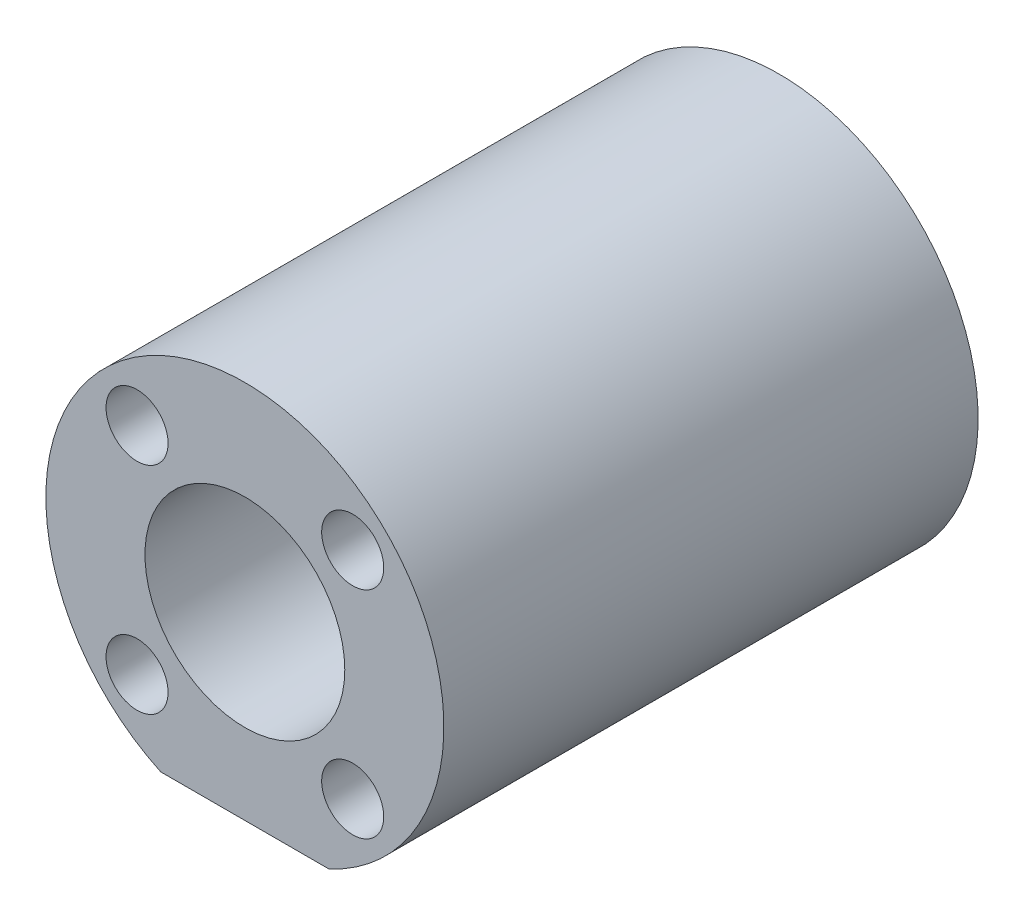
SolidWorks part; units mm, degrees
ref_plane "Front Plane" through (0, 0, 0) normal (0, 0, 1) x (1, 0, 0)
ref_plane "Top Plane" through (0, 0, 0) normal (0, 1, 0) x (1, 0, 0)
ref_plane "Right Plane" through (0, 0, 0) normal (1, 0, 0) x (0, 0, -1)
sketch "Sketch1" plane through (0, 0, 0) normal (0, 0, 1) x (1, 0, 0)
  line L0 (0, 0) -> (0, -18.584) construction
  line L1 (-3.9986, -8.575) -> (3.9986, -8.575)
  line L2 (3.9986, -8.575) -> (59.8984, 17.4915) construction
  arc A0 (-3.9986, -8.575) -> (3.9986, -8.575) centre (0, 0) cw
  circle A1 centre (0, 0) radius 4.75
  dimension "D2" = 9.4615
  dimension "D4" = 9.5
  dimension "D1" = 25
  dimension "D3" = 8.575
extrude "Boss-Extrude1" add sketch "Sketch1" along normal blind 25.4
sketch "Sketch3" plane through (0, 0, 25.4) normal (0, 0, -1) x (-1, 0, 0)
  line L0 (0, 0) -> (5.1265, -5.1265) construction
  line L1 (3.9986, -8.575) -> (0, 0) construction
  line L2 (0, 0) -> (-3.9986, -8.575) construction
  line L3 (0, 0) -> (0, -13.7827) construction
  circle A0 centre (5.1265, -5.1265) radius 1.475
  circle A1 centre (0, 0) radius 4 construction
  circle A2 centre (5.1265, -5.1265) radius 2.75 construction
  circle A3 centre (-5.1265, -5.1265) radius 1.475
  circle A4 centre (-5.1265, 5.1265) radius 1.475
  circle A5 centre (5.1265, 5.1265) radius 1.475
  point P10 (-20.1463, -0.2179)
  point P12 (0, 0)
  point P20 (0, 0)
  dimension "D3" = 2.95
  dimension "D5" = 8
  dimension "D6" = 5.5
  dimension "D1" = 50
  dimension "D2" = 7.25
  dimension "D4" = 45
  dimension "D7" = 4
extrude "Cut-Extrude1" cut sketch "Sketch3" along normal blind 19.05
equation "\"D2@Sketch1\"=0.745/2"
equation "\"D4@Sketch1\"=9.5mm"
equation "\"D2@Sketch3\"=7.25mm"
equation "\"D3@Sketch3\"=2.95mm"
equation "\"D5@Sketch3\"=8mm"
equation "\"D6@Sketch3\"=5.5mm"
